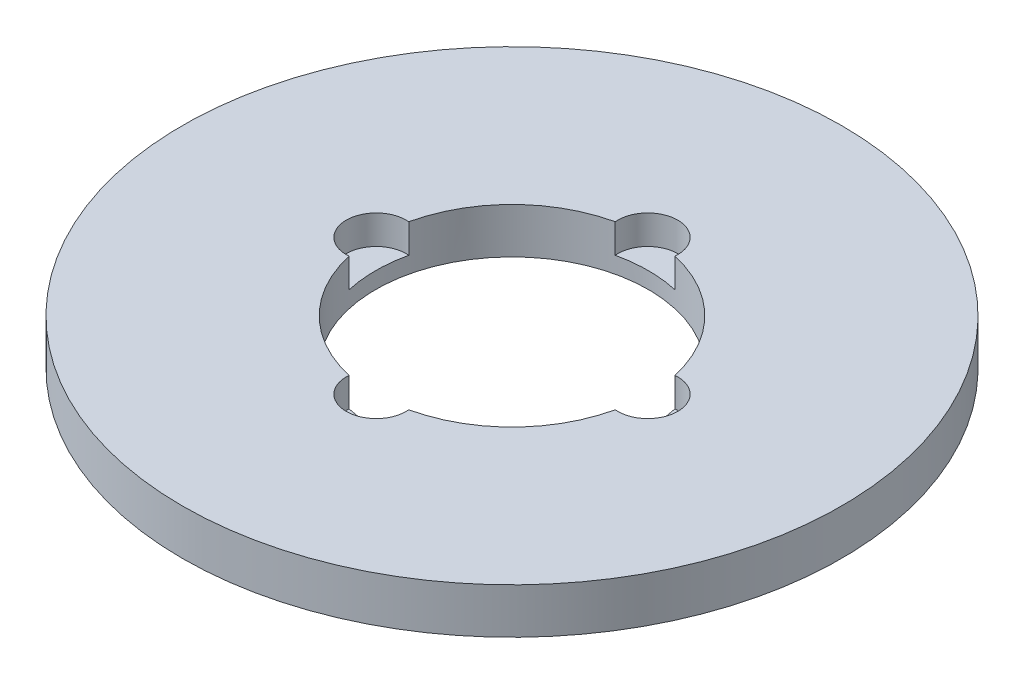
SolidWorks part; units mm, degrees
ref_plane "Front Plane" through (0, 0, 0) normal (0, 0, 1) x (1, 0, 0)
ref_plane "Top Plane" through (0, 0, 0) normal (0, 1, 0) x (1, 0, 0)
ref_plane "Right Plane" through (0, 0, 0) normal (1, 0, 0) x (0, 0, -1)
sketch "Sketch1" plane through (0, 0, 0) normal (0, 1, 0) x (1, 0, 0)
  circle A0 centre (0, 0) radius 72.5
  dimension "FLANGE_OD" = 145
extrude "Boss-Extrude1" add sketch "Sketch1" along normal blind 10
sketch "Sketch2" plane through (0, 0, 0) normal (0, 1, 0) x (1, 0, 0)
  circle A0 centre (0, 0) radius 30
  dimension "BORE_D" = 60
extrude "Cut-Extrude1" cut sketch "Sketch2" along normal through all
sketch "Sketch3" plane through (0, 10, 0) normal (0, 1, 0) x (1, 0, 0)
  circle A0 centre (0, 0) radius 29.8724 construction
  circle A1 centre (-29.8724, 0) radius 6.5875
  dimension "BOLT_D" = 13.175
  dimension "BOLT_PCD" = 59.7448
extrude "Cut-Extrude2" cut sketch "Sketch3" against normal blind 6.3944
pattern_circular "CirPattern1" count 4 over 360 about axis through (0, 0, 0) along (0, 1, 0) of "Cut-Extrude2"
